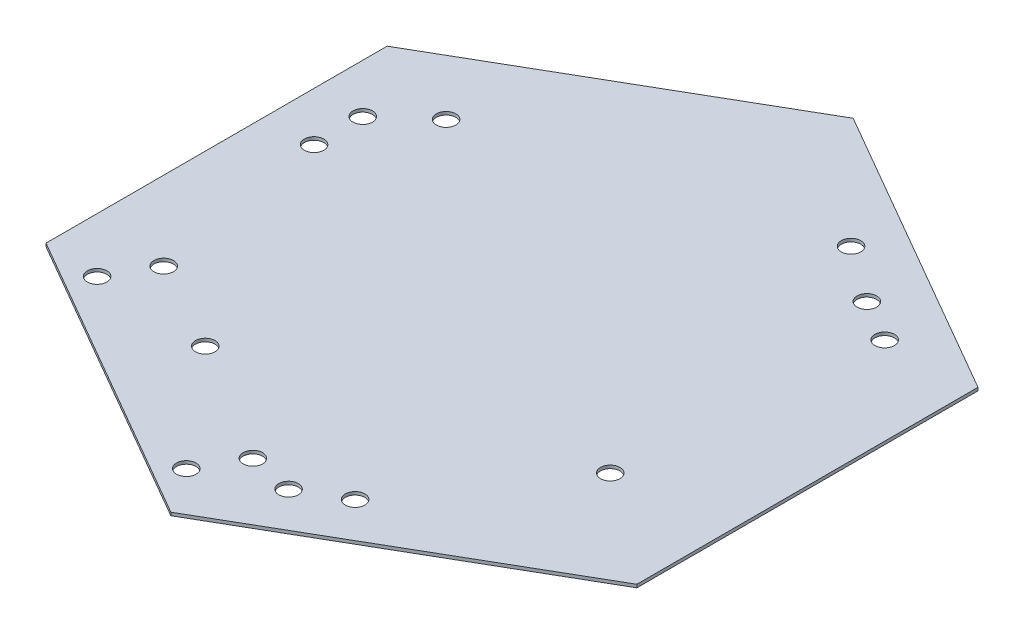
SolidWorks part; units mm, degrees
material "5052-H32"
ref_plane "Front Plane" through (0, 0, 0) normal (0, 0, 1) x (1, 0, 0)
ref_plane "Top Plane" through (0, 0, 0) normal (0, 1, 0) x (1, 0, 0)
ref_plane "Right Plane" through (0, 0, 0) normal (1, 0, 0) x (0, 0, -1)
sketch "Sketch1" plane through (0, 0, 0) normal (0, 1, 0) x (1, 0, 0)
  line L0 (10.1478, -68.3765) -> (21.1463, -62.0265) construction
  line L1 (0, 88.9) -> (-76.9897, 44.45)
  line L2 (-76.9897, 44.45) -> (-76.9897, -44.45)
  line L3 (-76.9897, -44.45) -> (0, -88.9)
  line L4 (0, -88.9) -> (76.9897, -44.45)
  line L5 (76.9897, -44.45) -> (76.9897, 44.45)
  line L6 (76.9897, 44.45) -> (0, 88.9)
  line L7 (21.1463, -62.0265) -> (27.4963, -73.025) construction
  line L8 (-64.2897, 25.4) -> (-64.2897, 12.7) construction
  line L9 (-64.2897, 12.7) -> (-76.9897, 12.7) construction
  line L10 (54.1419, 42.9765) -> (43.1434, 49.3265) construction
  line L11 (43.1434, 49.3265) -> (49.4934, 60.325) construction
  circle A0 centre (0, 0) radius 76.9897 construction
  circle A1 centre (10.1478, -68.3765) radius 2.54
  circle A2 centre (21.1463, -62.0265) radius 2.54
  circle A3 centre (-64.2897, 25.4) radius 2.54
  circle A4 centre (-64.2897, 12.7) radius 2.54
  circle A5 centre (54.1419, 42.9765) radius 2.54
  circle A6 centre (43.1434, 49.3265) radius 2.54
  point P13 (38.4948, -66.675)
  point P28 (0, 0)
  dimension "D2" = 5.08
  dimension "D3" = 12.7
  dimension "D4" = 12.7
  dimension "D1" = 177.8
  dimension "D5" = 12.7
  dimension "D6" = 3
extrude "Boss-Extrude1" add sketch "Sketch1" along normal blind 0.8128
sketch "Sketch2" plane through (0, 0.8128, 0) normal (0, 1, 0) x (1, 0, 0)
  line L1 (17.6188, -76.1634) -> (79.2138, 30.5223) construction
  line L2 (17.6188, -76.1634) -> (-83.5676, -17.7434) construction
  line L3 (-83.5676, -17.7434) -> (-21.9726, 88.9423) construction
  line L4 (79.2138, 30.5223) -> (-21.9726, 88.9423) construction
  line L7 (-76.9897, -44.45) -> (0, -88.9) construction
  circle A0 centre (28.6206, 59.7323) radius 2.54
  circle A1 centre (48.4163, -22.8205) radius 2.54
  circle A2 centre (-52.7701, 35.5995) radius 2.54
  circle A3 centre (-32.9744, -46.9534) radius 2.54
  dimension "D5" = 5.08
  dimension "D1" = 123.19
  dimension "D2" = 116.84
  dimension "D3" = 57.15
  dimension "D4" = 53.34
extrude "Cut-Extrude1" cut sketch "Sketch2" against normal through all
sketch "Sketch3" plane through (0, 0.8128, 0) normal (0, 1, 0) x (1, 0, 0)
  line L0 (-62.8161, -45.3007) -> (-65.9911, -50.8) construction
  line L2 (-76.9897, -44.45) -> (0, -88.9) construction
  line L3 (-62.8161, -45.3007) -> (-7.8235, -77.0507) construction
  line L4 (-35.3198, -61.1757) -> (-38.4948, -66.675) construction
  line L5 (-56.4661, -34.3022) -> (-62.8161, -45.3007) construction
  line L6 (-56.4661, -34.3022) -> (-1.4735, -66.0522) construction
  circle A1 centre (-7.8235, -77.0507) radius 2.54
  circle A2 centre (-62.8161, -45.3007) radius 2.54
  circle A3 centre (-56.4661, -34.3022) radius 2.54
  circle A4 centre (-1.4735, -66.0522) radius 2.54
  dimension "D1" = 5.08
  dimension "D2" = 6.35
  dimension "D3" = 63.5
  dimension "D4" = 12.7
extrude "Cut-Extrude2" cut sketch "Sketch3" against normal through all
